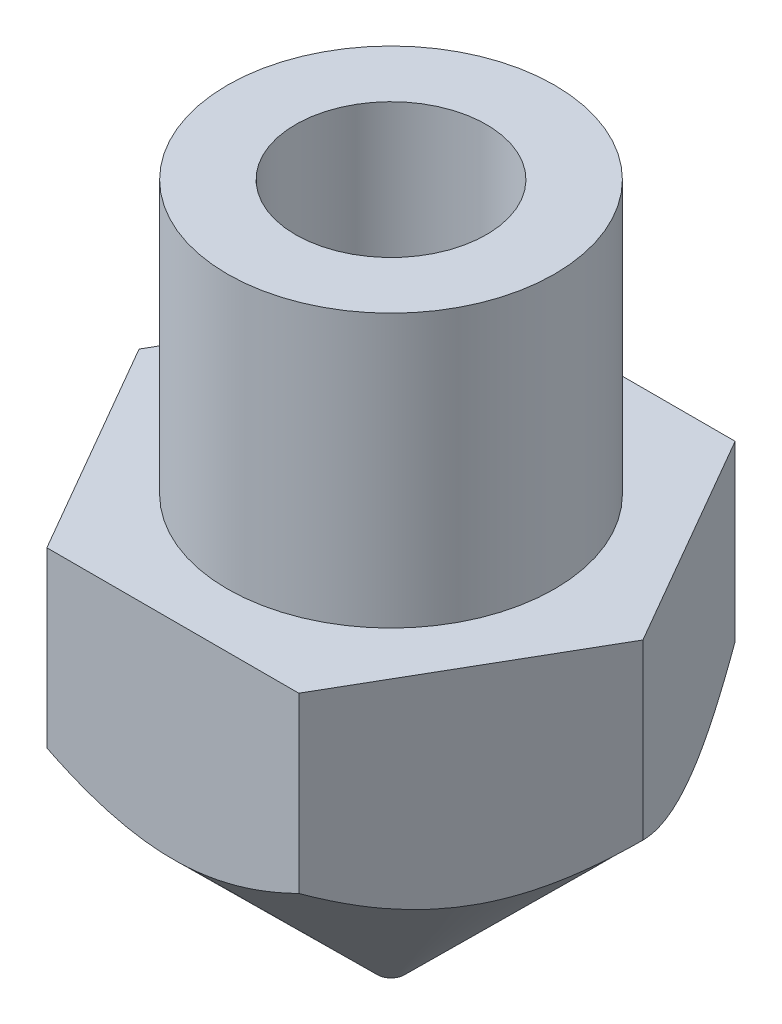
SolidWorks part; units mm, degrees
ref_plane "Front Plane" through (0, 0, 0) normal (0, 0, 1) x (1, 0, 0)
ref_plane "Top Plane" through (0, 0, 0) normal (0, 1, 0) x (1, 0, 0)
ref_plane "Right Plane" through (0, 0, 0) normal (1, 0, 0) x (0, 0, -1)
sketch "Sketch1" plane through (0, 0, 0) normal (0, 0, 1) x (1, 0, 0)
  line L0 (0, 0) -> (0, 4.5) construction
  line L1 (0, 0) -> (-0.2, 0) construction
  line L2 (-0.2, 0) -> (-0.25, 0)
  line L3 (-0.25, 0) -> (-4.8, 4.5)
  line L4 (-4.8, 4.5) -> (-1.75, 4.5)
  line L5 (-1.75, 4.5) -> (-1.75, 2.6847)
  line L6 (-1.75, 2.6847) -> (-0.2, 0)
  dimension "D1" = 4.8
  dimension "D2" = 0.25
  dimension "D3" = 0.2
  dimension "D4" = 4.5
  dimension "D5" = 1.75
  dimension "D6" = 30
revolve "Revolve1" add sketch "Sketch1" angle 360 about L0
sketch "Sketch2" plane through (0, 4.5, 0) normal (0, 1, 0) x (1, 0, 0)
  line L1 (2.3094, -4) -> (4.6188, 0)
  line L2 (4.6188, 0) -> (2.3094, 4)
  line L3 (2.3094, 4) -> (-2.3094, 4)
  line L4 (-2.3094, 4) -> (-4.6188, 0)
  line L5 (-4.6188, 0) -> (-2.3094, -4)
  line L6 (-2.3094, -4) -> (2.3094, -4)
  circle A0 centre (0, 0) radius 4 construction
  dimension "D1" = 8
extrude "Boss-Extrude1" add sketch "Sketch2" along normal blind 3
sketch "Sketch3" plane through (0, 7.5, 0) normal (0, 1, 0) x (1, 0, 0)
  line L6 (-2.3094, -4) -> (2.3094, -4)
  line L7 (2.3094, -4) -> (4.6188, 0)
  line L8 (4.6188, 0) -> (2.3094, 4)
  line L9 (2.3094, 4) -> (-2.3094, 4)
  line L10 (-2.3094, 4) -> (-4.6188, 0)
  line L11 (-4.6188, 0) -> (-2.3094, -4)
  line L12 (-2.3094, -4) -> (2.3094, -4)
  line L13 (2.3094, -4) -> (4.6188, 0)
  line L14 (4.6188, 0) -> (2.3094, 4)
  line L15 (2.3094, 4) -> (-2.3094, 4)
  line L16 (-2.3094, 4) -> (-4.6188, 0)
  line L17 (-4.6188, 0) -> (-2.3094, -4)
  circle A0 centre (0, 0) radius 5.4617
  dimension "D1" = 0
extrude "Cut-Extrude1" cut sketch "Sketch3" against normal blind 10
ref_axis "Axis1" through (0, 2.6847, 0) along (0, -1, 0)
ref_plane "Plane1" through (0, 4.3208, 0) normal (0, -1, 0) x (-1, 0, 0)
sketch "Sketch4" plane through (0, 7.5, 0) normal (0, 1, 0) x (1, 0, 0)
  circle A0 centre (0, 0) radius 1.75
  dimension "D1" = 3.5
extrude "Cut-Extrude2" cut sketch "Sketch4" against normal up to surface (3.1792 mm away) up to plane "Plane1"
sketch "Sketch5" plane through (0, 7.5, 0) normal (0, 1, 0) x (1, 0, 0)
  circle A0 centre (0, 0) radius 3
  circle A1 centre (0, 0) radius 1.75
  dimension "D1" = 3.5
  dimension "D2" = 6
extrude "Boss-Extrude2" add sketch "Sketch5" along normal blind 5
cosmetic thread "Rosca cosmética3" parameters "D2"=4.891
